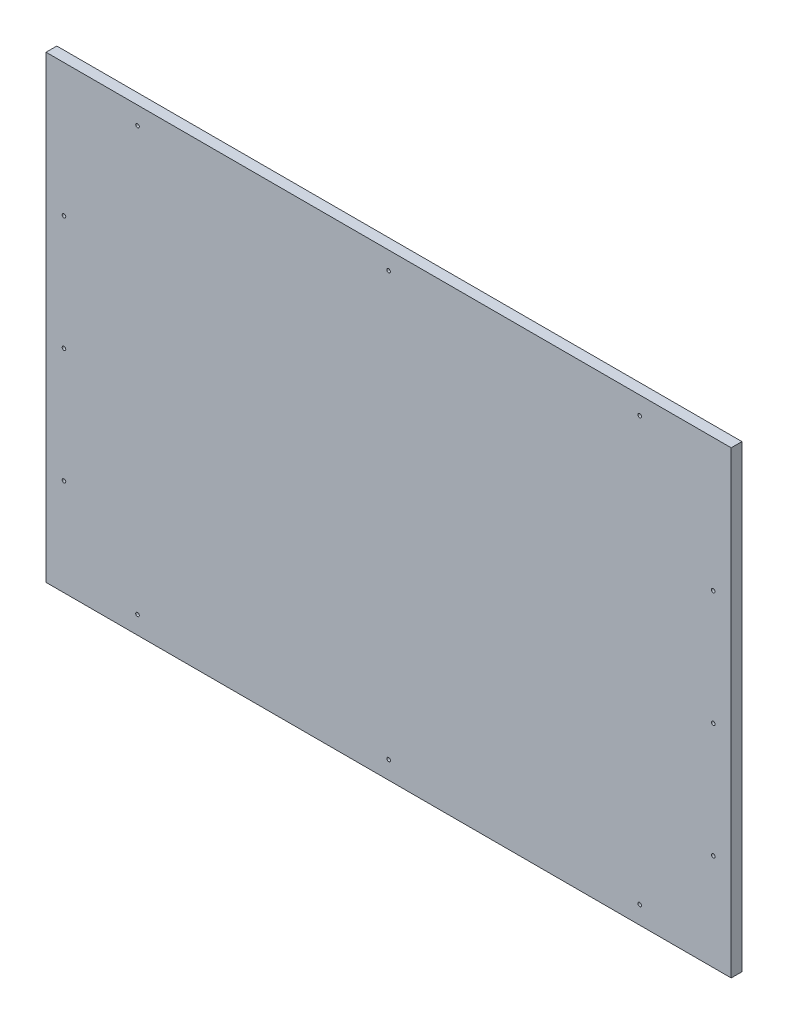
SolidWorks part; units mm, degrees
material "西洋杉"
ref_plane "正面" through (0, 0, 0) normal (0, 0, 1) x (1, 0, 0)
ref_plane "平面" through (0, 0, 0) normal (0, 1, 0) x (1, 0, 0)
ref_plane "右側面" through (0, 0, 0) normal (1, 0, 0) x (0, 0, -1)
sketch "ｽｹｯﾁ1" plane through (0, 0, 0) normal (0, 0, 1) x (1, 0, 0)
  line L1 (-477.5, 320) -> (477.5, 320)
  line L2 (-477.5, 320) -> (-477.5, -320)
  line L3 (-477.5, -320) -> (477.5, -320)
  line L4 (477.5, 320) -> (477.5, -320)
  line L5 (-477.5, 320) -> (477.5, -320) construction
  line L6 (-477.5, -320) -> (477.5, 320) construction
  point P0 (0, 0)
  dimension "D1" = 640
  dimension "D2" = 955
extrude "ﾎﾞｽ - 押し出し1" add sketch "ｽｹｯﾁ1" along normal blind 15
sketch "ｽｹｯﾁ2" plane through (0, 0, 15) normal (0, 0, 1) x (1, 0, 0)
  line L0 (-452.5, 295) -> (-452.5, -295) construction
  line L1 (-452.5, -295) -> (452.5, -295) construction
  line L2 (452.5, -295) -> (452.5, 295) construction
  line L3 (452.5, 295) -> (-452.5, 295) construction
  line L4 (-477.5, 320) -> (-477.5, -320) construction
  line L5 (477.5, 320) -> (-477.5, 320) construction
  line L6 (477.5, -320) -> (477.5, 320) construction
  line L7 (-477.5, -320) -> (477.5, -320) construction
  line L8 (-477.5, -320) -> (477.5, -320) construction
  line L9 (-477.5, 320) -> (-477.5, -320) construction
  circle A0 centre (-452.5, 135) radius 2.5
  circle A1 centre (-452.5, -25) radius 2.5
  circle A2 centre (-452.5, -185) radius 2.5
  circle A3 centre (452.5, -25) radius 2.5
  circle A4 centre (452.5, -185) radius 2.5
  circle A5 centre (452.5, 135) radius 2.5
  circle A6 centre (0, 295) radius 2.5
  circle A7 centre (-350, 295) radius 2.5
  circle A8 centre (350, 295) radius 2.5
  dimension "D5" = 5
  dimension "D11" = 5
  dimension "D12" = 5
  dimension "D13" = 5
  dimension "D14" = 350
  dimension "D15" = 350
  dimension "D1" = 25
  dimension "D2" = 25
  dimension "D3" = 25
  dimension "D4" = 25
  dimension "D6" = 160
  dimension "D7" = 640
  dimension "D8" = 955
  dimension "D9" = 3
  dimension "D10" = 2
extrude "ｶｯﾄ - 押し出し1" cut sketch "ｽｹｯﾁ2" against normal through all and the other way through all contours A2 | A4 | A3 | A1 | A0 | A5 region at (-452.5, -185, 15) region at (452.5, -25, 15) region at (452.5, -185, 15)
extrude "ｶｯﾄ - 押し出し2" cut sketch "ｽｹｯﾁ2<3>" against normal through all contours A7 | A6 | A8
sketch "ｽｹｯﾁ2<3>" plane through (0, 0, 15) normal (0, 0, 1) x (1, 0, 0) same geometry as "ｽｹｯﾁ2"
mirror "ﾐﾗｰ1" about plane through (0, 0, 0) normal (0, 1, 0) of "ｶｯﾄ - 押し出し2"
